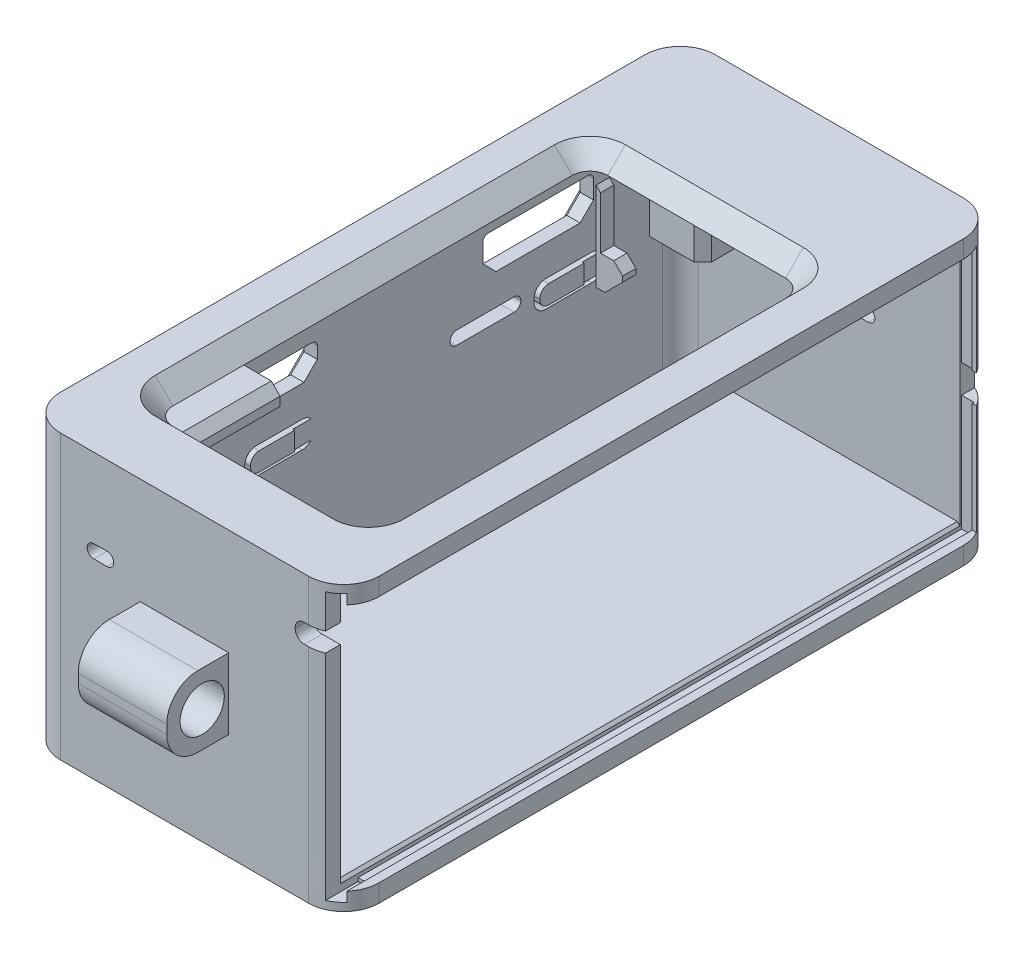
SolidWorks part; units mm, degrees
ref_plane "前视基准面" through (0, 0, 0) normal (0, 0, 1) x (1, 0, 0)
ref_plane "上视基准面" through (0, 0, 0) normal (0, 1, 0) x (1, 0, 0)
ref_plane "右视基准面" through (0, 0, 0) normal (1, 0, 0) x (0, 0, -1)
sketch "草图1" plane through (0, 0, 0) normal (1, 0, 0) x (0, 0, -1)
  line L1 (-54.0501, 29.0398) -> (19.9499, 29.0398)
  line L2 (-54.0501, 29.0398) -> (-54.0501, -2.9602)
  line L3 (-54.0501, -2.9602) -> (19.9499, -2.9602)
  line L4 (19.9499, 29.0398) -> (19.9499, -2.9602)
  dimension "D1" = 74
  dimension "D2" = 32
extrude "凸台-拉伸1" add sketch "草图1" along normal blind 36
sketch "草图2" plane through (36, 0, 0) normal (1, 0, 0) x (0, 0, -1)
  line L8 (17.9499, -0.9602) -> (17.9499, 27.0398)
  line L9 (-52.0501, -0.9602) -> (17.9499, -0.9602)
  line L10 (-52.0501, 27.0398) -> (-52.0501, -0.9602)
  line L11 (17.9499, 27.0398) -> (-52.0501, 27.0398)
  line L12 (17.9499, -0.9602) -> (17.9499, 27.0398)
  line L13 (-52.0501, -0.9602) -> (17.9499, -0.9602)
  line L14 (-52.0501, 27.0398) -> (-52.0501, -0.9602)
  line L15 (17.9499, 27.0398) -> (-52.0501, 27.0398)
  dimension "D1" = 2
extrude "切除-拉伸1" cut sketch "草图2" against normal blind 34
fillet "圆角1" radius 2 2 edges at (2, 13.0398, -17.9499) (2, 13.0398, 52.0501)
fillet "圆角2" radius 4 4 edges at (0, 13.0398, -19.9499) (0, 13.0398, 54.0501) (36, 13.0398, 54.0501) (36, 13.0398, -19.9499)
sketch "草图3" plane through (0, 29.0398, 0) normal (0, 1, 0) x (1, 0, 0)
  line L0 (32, 19.9499) -> (4, 19.9499) construction
  line L1 (29.8, 4.0599) -> (5.7, 4.0599)
  line L2 (29.8, 4.0599) -> (29.8, -45.0601)
  line L3 (29.8, -45.0601) -> (5.7, -45.0601)
  line L4 (5.7, 4.0599) -> (5.7, -45.0601)
  line L5 (36, 15.9499) -> (36, -50.0501) construction
  line L6 (32, -54.0501) -> (4, -54.0501) construction
  line L7 (0, 15.9499) -> (0, -50.0501) construction
  dimension "D1" = 15.89
  dimension "D2" = 6.2
  dimension "D3" = 8.99
  dimension "D4" = 5.7
extrude "切除-拉伸2" cut sketch "草图3" against normal blind 10
fillet "圆角3" radius 2 4 edges at (5.7, 28.0398, 45.0601) (29.8, 28.0398, 45.0601) (29.8, 28.0398, -4.0599) (5.7, 28.0398, -4.0599)
chamfer "倒角1" distance 2 angle 45 8 edges at (17.75, 29.0398, 45.0601) (29.2142, 29.0398, 44.4744) (6.2858, 29.0398, 44.4744) (29.8, 29.0398, 20.5001) (5.7, 29.0398, 20.5001) (29.2142, 29.0398, -3.4741) (6.2858, 29.0398, -3.4741) (17.75, 29.0398, -4.0599)
sketch "草图4" plane through (0, 0, 0) normal (-1, 0, 0) x (0, 0, 1)
  line L0 (-15.9499, 29.0398) -> (50.0501, 29.0398) construction
  line L1 (-8.1499, 22.4398) -> (4.3501, 22.4398)
  line L2 (-8.1499, 22.4398) -> (-8.1499, 18.2398)
  line L3 (-8.1499, 18.2398) -> (4.3501, 18.2398)
  line L4 (4.3501, 22.4398) -> (4.3501, 18.2398)
  line L5 (23.0501, 21.6812) -> (31.2501, 21.6812)
  line L6 (23.0501, 21.6812) -> (23.0501, 18.2398)
  line L7 (23.0501, 18.2398) -> (31.2501, 18.2398)
  line L8 (31.2501, 21.6812) -> (31.2501, 18.2398)
  line L9 (35.5501, 21.6398) -> (43.7501, 21.6398)
  line L10 (35.5501, 21.6398) -> (35.5501, 18.2398)
  line L11 (35.5501, 18.2398) -> (43.7501, 18.2398)
  line L12 (43.7501, 21.6398) -> (43.7501, 18.2398)
  line L13 (-9.2499, 14.7398) -> (-1.4499, 14.7398)
  line L14 (-9.2499, 14.7398) -> (-9.2499, 11.7398)
  line L15 (-9.2499, 11.7398) -> (-1.4499, 11.7398)
  line L16 (-1.4499, 14.7398) -> (-1.4499, 11.7398)
  line L17 (23.4501, 14.7398) -> (31.2501, 14.7398)
  line L18 (23.4501, 14.7398) -> (23.4501, 11.7398)
  line L19 (23.4501, 11.7398) -> (31.2501, 11.7398)
  line L20 (31.2501, 14.7398) -> (31.2501, 11.7398)
  line L21 (33.8696, 14.7398) -> (43.3696, 14.7398)
  line L22 (33.8696, 14.7398) -> (33.8696, 11.5398)
  line L23 (33.8696, 11.5398) -> (43.3696, 11.5398)
  line L24 (43.3696, 14.7398) -> (43.3696, 11.5398)
  line L25 (54.0501, 29.0398) -> (54.0501, -2.9602) construction
  line L27 (8.0501, 14.7398) -> (0.0501, 14.7398)
  line L28 (8.0501, 14.7398) -> (8.0501, 13.2398)
  line L29 (8.0501, 13.2398) -> (0.0501, 13.2398)
  line L30 (0.0501, 14.7398) -> (0.0501, 13.2398)
  dimension "D1" = 14.3
  dimension "D2" = 3.2
  dimension "D3" = 3
  dimension "D4" = 7.8
  dimension "D5" = 7.8
  dimension "D6" = 8.2
  dimension "D7" = 8.2
  dimension "D8" = 3.4
  dimension "D9" = 12.5
  dimension "D10" = 4.2
  dimension "D11" = 10.8
  dimension "D12" = 10.3
  dimension "D13" = 4.3
  dimension "D14" = 18.7
  dimension "D15" = 9.5
  dimension "D16" = 55.5
  dimension "D17" = 1.5
  dimension "D18" = 8
  dimension "D19" = 1.5
extrude "切除-拉伸3" cut sketch "草图4" against normal blind 10
fillet "圆角8" radius 0.75 4 edges at (1, 14.7398, 0.0501) (1, 14.7398, 8.0501) (1, 13.2398, 8.0501) (1, 13.2398, 0.0501)
sketch "草图5" plane through (2, 0, 0) normal (1, 0, 0) x (0, 0, -1)
  line L0 (-23.4501, 11.7398) -> (-23.4501, 14.7398) construction
  line L1 (-23.4501, 14.2898) -> (-30.8001, 14.2898)
  line L2 (-23.4501, 14.2898) -> (-23.4501, 12.1898)
  line L3 (-23.4501, 12.1898) -> (-30.8001, 12.1898)
  line L4 (-30.8001, 14.2898) -> (-30.8001, 12.1898)
  line L6 (1.8999, 12.1898) -> (9.2499, 12.1898)
  line L7 (1.8999, 12.1898) -> (1.8999, 14.2898)
  line L8 (1.8999, 14.2898) -> (9.2499, 14.2898)
  line L9 (9.2499, 12.1898) -> (9.2499, 14.2898)
  line L10 (-23.4501, 14.7398) -> (-31.2501, 14.7398) construction
  line L11 (-31.2501, 11.7398) -> (-23.4501, 11.7398) construction
  line L12 (-31.2501, 14.7398) -> (-31.2501, 11.7398) construction
  line L13 (9.2499, 14.7398) -> (1.4499, 14.7398) construction
  line L14 (1.4499, 11.7398) -> (9.2499, 11.7398) construction
  line L16 (1.4499, 14.7398) -> (1.4499, 11.7398) construction
  line L17 (9.2499, 11.7398) -> (9.2499, 14.7398) construction
  dimension "D1" = 0.45
  dimension "D2" = 0.45
  dimension "D3" = 0.45
  dimension "D4" = 0.45
  dimension "D5" = 0.45
  dimension "D7" = 0.45
extrude "凸台-拉伸2" add sketch "草图5" against normal blind 1.2
sketch "草图6" plane through (0.8, 0, 0) normal (-1, 0, 0) x (0, 0, 1)
  line L0 (-1.8999, 12.1898) -> (-9.2499, 12.1898) construction
  line L1 (-6.8999, 14.2898) -> (-1.8999, 14.2898)
  line L2 (-6.8999, 14.2898) -> (-6.8999, 12.1898)
  line L3 (-6.8999, 12.1898) -> (-1.8999, 12.1898)
  line L4 (-1.8999, 14.2898) -> (-1.8999, 12.1898)
  line L5 (30.8001, 12.1898) -> (23.4501, 12.1898) construction
  line L6 (30.8001, 14.2898) -> (25.8001, 14.2898)
  line L7 (30.8001, 14.2898) -> (30.8001, 12.1898)
  line L8 (30.8001, 12.1898) -> (25.8001, 12.1898)
  line L9 (25.8001, 14.2898) -> (25.8001, 12.1898)
  line L10 (-1.8999, 14.2898) -> (-1.8999, 12.1898) construction
  line L11 (-9.2499, 14.2898) -> (-1.8999, 14.2898) construction
  point P4 (-6.8999, 14.2898)
  point P18 (25.8001, 12.1898)
  dimension "D1" = 5
  dimension "D2" = 5
extrude "凸台-拉伸3" add sketch "草图6" along normal blind 1.5 and the other way blind 1.4
fillet "圆角4" radius 0.6 10 edges at (1, 11.5398, 33.8696) (1, 14.7398, 33.8696) (1, 14.7398, 43.3696) (1, 11.5398, 43.3696) (1, 21.6398, 35.5501) (1, 21.6398, 43.7501) (1, 21.6812, 31.2501) (1, 21.6812, 23.0501) (1, 22.4398, -8.1499) (1, 22.4398, 4.3501)
chamfer "倒角2" distance 1.5 angle 45 6 edges at (1, 18.2398, 43.7501) (1, 18.2398, 35.5501) (1, 18.2398, 31.2501) (1, 18.2398, 23.0501) (1, 18.2398, 4.3501) (1, 18.2398, -8.1499)
fillet "圆角5" radius 1 8 edges at (0.05, 12.1898, 25.8001) (0.05, 14.2898, 25.8001) (0.75, 12.1898, 30.8001) (0.75, 14.2898, 30.8001) (0.75, 12.1898, -1.8999) (0.75, 14.2898, -1.8999) (0.05, 12.1898, -6.8999) (0.05, 14.2898, -6.8999)
chamfer "倒角10" distance 0.2 angle 45 16 edges at (-0.7, 12.1898, 28.3001) (-0.7, 12.4827, 30.5072) (-0.7, 12.4827, 26.093) (-0.7, 13.9969, 30.5072) (-0.7, 13.9969, 26.093) (-0.7, 14.2898, 28.3001) (-0.7, 12.1898, -4.3999) (-0.7, 12.4827, -2.1928) (-0.7, 13.9969, -2.1928) (-0.7, 14.2898, -4.3999) (-0.7, 12.4827, -6.607) (-0.7, 13.9969, -6.607) (-0.7, 13.2398, 30.8001) (-0.7, 13.2398, 25.8001) (-0.7, 13.2398, -1.8999) (-0.7, 13.2398, -6.8999)
fillet "圆角6" radius 1.3 8 edges at (1, 14.7398, -1.4499) (1, 11.7398, -1.4499) (1, 11.7398, -9.2499) (1, 14.7398, -9.2499) (1, 14.7398, 23.4501) (1, 11.7398, 23.4501) (1, 11.7398, 31.2501) (1, 14.7398, 31.2501)
chamfer "倒角4" distance 0.5 angle 45 54 edges at (0, 11.7398, -5.3499) (0, 12.1206, -1.8306) (0, 12.1206, -8.8691) (0, 14.359, -1.8306) (0, 14.359, -8.8691) (0, 14.7398, -5.3499) (0, 18.9898, -7.3999) (0, 18.2398, -1.8999) (0, 18.9898, 3.6001) (0, 20.7898, 4.3501) (0, 20.7898, -8.1499) (0, 22.2641, 4.1744) (0, 22.2641, -7.9741) (0, 22.4398, -1.8999) (0, 11.5398, 38.6196) (0, 11.7155, 43.1938) (0, 11.7155, 34.0453) (0, 13.1398, 43.3696) (0, 13.1398, 33.8696) (0, 14.5641, 43.1938) (0, 14.5641, 34.0453) (0, 14.7398, 38.6196) (0, 11.7398, 27.3501) (0, 12.1206, 30.8694) (0, 12.1206, 23.8309) (0, 14.359, 30.8694) (0, 14.359, 23.8309) (0, 14.7398, 27.3501) (0, 20.4105, 23.0501) (0, 21.5055, 23.2259) (0, 21.6812, 27.1501) (0, 21.5055, 31.0744) (0, 18.9898, 23.8001) (0, 18.2398, 27.1501) (0, 18.9898, 30.5001) (0, 20.4105, 31.2501) (0, 18.9898, 43.0001) (0, 18.2398, 39.6501) (0, 18.9898, 36.3001) (0, 20.3898, 35.5501) (0, 21.4641, 35.7259) (0, 21.6398, 39.6501) (0, 20.3898, 43.7501) (0, 21.4641, 43.5744) (0, 13.4595, 7.8305) (0, 13.2398, 4.0501) (0, 13.4595, 0.2698) (0, 14.5201, 7.8305) (0, 14.7398, 4.0501) (0, 14.5201, 0.2698) (0, 13.2398, -1.4499) (0, 13.2398, -9.2499) (0, 13.2398, 31.2501) (0, 13.2398, 23.4501)
sketch "草图7" plane through (2, 0, 0) normal (1, 0, 0) x (0, 0, -1)
  line L0 (15.9499, 27.0398) -> (-50.0501, 27.0398) construction
  line L1 (-46.0501, 21.0398) -> (-44.5501, 21.0398)
  line L2 (-46.0501, 21.0398) -> (-46.0501, 11.0398)
  line L3 (-46.0501, 11.0398) -> (-44.5501, 11.0398)
  line L4 (-44.5501, 21.0398) -> (-44.5501, 11.0398)
  line L5 (8.4499, 21.0398) -> (9.9499, 21.0398)
  line L6 (8.4499, 21.0398) -> (8.4499, 11.0398)
  line L7 (8.4499, 11.0398) -> (9.9499, 11.0398)
  line L8 (9.9499, 21.0398) -> (9.9499, 11.0398)
  line L11 (17.9499, -0.9602) -> (17.9499, 27.0398) construction
  line L12 (-52.0501, 27.0398) -> (-52.0501, -0.9602) construction
  dimension "D1" = 6
  dimension "D2" = 10
  dimension "D3" = 1.5
  dimension "D4" = 1.5
  dimension "D5" = 8
  dimension "D6" = 6
extrude "凸台-拉伸4" add sketch "草图7" along normal blind 0.5
sketch "草图10" plane through (2.5, 0, 0) normal (1, 0, 0) x (0, 0, -1)
  line L1 (-46.0501, 11.0398) -> (-44.5501, 11.0398)
  line L2 (-46.0501, 11.0398) -> (-46.0501, 14.6398)
  line L3 (-46.0501, 14.6398) -> (-44.5501, 14.6398)
  line L4 (-44.5501, 11.0398) -> (-44.5501, 14.6398)
  line L7 (8.4499, 11.0398) -> (9.9499, 11.0398)
  line L8 (8.4499, 11.0398) -> (8.4499, 14.6398)
  line L9 (8.4499, 14.6398) -> (9.9499, 14.6398)
  line L10 (9.9499, 11.0398) -> (9.9499, 14.6398)
  dimension "D1" = 3.6
extrude "凸台-拉伸6" add sketch "草图10" along normal blind 2.5
chamfer "倒角7" distance 1 angle 45 2 edges at (5, 14.6398, -9.1999) (5, 14.6398, 45.3001)
chamfer "倒角8" distance 2 angle 45 2 edges at (5, 11.0398, 45.3001) (5, 11.0398, -9.1999)
chamfer "倒角5" distance 0.5 angle 45 2 edges at (2.5, 21.0398, 45.3001) (2.5, 21.0398, -9.1999)
sketch "草图8" plane through (2, 0, 0) normal (1, 0, 0) x (0, 0, -1)
  line L0 (15.9499, 29.0398) -> (-50.0501, 29.0398) construction
  line L1 (-44.2501, 22.2398) -> (-32.2501, 22.2398)
  line L2 (-44.2501, 22.2398) -> (-44.2501, 24.2398)
  line L3 (-44.2501, 24.2398) -> (-32.2501, 24.2398)
  line L4 (-32.2501, 22.2398) -> (-32.2501, 24.2398)
  line L5 (-54.0501, -2.9602) -> (-54.0501, 29.0398) construction
  dimension "D1" = 4.8
  dimension "D2" = 2
  dimension "D3" = 12
  dimension "D4" = 9.8
extrude "凸台-拉伸5" add sketch "草图8" along normal blind 5
chamfer "倒角6" distance 1 angle 45 1 edges at (7, 24.2398, 38.2501)
sketch "草图12" plane through (0, 0, 54.0501) normal (0, 0, 1) x (1, 0, 0)
  line L0 (4, -0.9602) -> (35.4641, -0.9602) construction
  line L1 (36, 27.0398) -> (33.6, 27.0398)
  line L2 (36, 27.0398) -> (36, -0.9602)
  line L3 (36, -0.9602) -> (33.6, -0.9602)
  line L4 (33.6, 27.0398) -> (33.6, -0.9602)
  dimension "D1" = 2.4
extrude "切除-拉伸5" cut sketch "草图12" against normal blind 10.8
sketch "草图11" plane through (0, -0.9602, 0) normal (0, 1, 0) x (1, 0, 0)
  line L0 (32, 19.9499) -> (4, 19.9499) construction
  line L1 (35, 17.9499) -> (33.6, 17.9499)
  line L2 (35, 17.9499) -> (35, -54.0501)
  line L3 (35, -54.0501) -> (33.6, -54.0501)
  line L4 (33.6, 17.9499) -> (33.6, -54.0501)
  line L5 (32, -54.0501) -> (4, -54.0501) construction
  line L6 (36, -50.0501) -> (36, 15.9499) construction
  dimension "D1" = 2
  dimension "D2" = 0
  dimension "D3" = 1
  dimension "D4" = 1.4
extrude "切除-拉伸4" cut sketch "草图11" against normal blind 0.7
sketch "草图13" plane through (0, 27.0398, 0) normal (0, -1, 0) x (1, 0, 0)
  line L10 (33.6, -17.9499) -> (35, -17.9499)
  line L11 (33.6, 54.0501) -> (33.6, -17.9499)
  line L12 (35, 54.0501) -> (33.6, 54.0501)
  line L13 (35, -17.9499) -> (35, 54.0501)
  line L14 (33.6, -17.9499) -> (35, -17.9499)
  line L15 (33.6, 54.0501) -> (33.6, -17.9499)
  line L16 (35, 54.0501) -> (33.6, 54.0501)
  line L17 (35, -17.9499) -> (35, 54.0501)
  dimension "D1" = 0
extrude "切除-拉伸6" cut sketch "草图13" against normal blind 0.7
sketch "草图14" plane through (0, -1.6602, 0) normal (0, 1, 0) x (1, 0, 0)
  line L1 (33.6, -54.0501) -> (35, -54.0501)
  line L2 (33.6, -54.0501) -> (33.6, -50.0501)
  line L3 (33.6, -50.0501) -> (35, -50.0501)
  line L4 (35, -54.0501) -> (35, -50.0501)
  line L5 (32, -54.0501) -> (4, -54.0501) construction
  line L6 (33.6, -53.7162) -> (33.6, 17.9499) construction
  dimension "D1" = 4
extrude "切除-拉伸7" cut sketch "草图14" against normal blind 0.4
sketch "草图15" plane through (0, 27.7398, 0) normal (0, -1, 0) x (1, 0, 0)
  line L3 (35, 50.0501) -> (35, 52.6959)
  line L4 (33.6, 50.0501) -> (35, 50.0501)
  line L5 (33.6, 53.7162) -> (33.6, 50.0501)
  line L7 (33.6, 50.0501) -> (35, 50.0501)
  line L8 (33.6, 53.7162) -> (33.6, 50.0501)
  line L10 (35, 50.0501) -> (35, 52.6959)
  arc A1 (35, 52.6959) -> (33.6, 53.7162) centre (32, 50.0501) ccw
  arc A2 (35, 52.6959) -> (33.6, 53.7162) centre (32, 50.0501) ccw
  dimension "D1" = 0
extrude "切除-拉伸8" cut sketch "草图15" against normal blind 0.4
sketch "草图16" plane through (0, 0, -17.9499) normal (0, 0, 1) x (1, 0, 0)
  line L0 (33.6, 28.1398) -> (33.6, -2.0602) construction
  line L1 (33.6, 27.7398) -> (35, 27.7398)
  line L2 (33.6, 27.7398) -> (33.6, -1.6602)
  line L3 (33.6, -1.6602) -> (35, -1.6602)
  line L4 (35, 27.7398) -> (35, -1.6602)
extrude "切除-拉伸9" cut sketch "草图16" against normal blind 0.2
chamfer "倒角9" distance 0.3 angle 45 2 edges at (33.6, 27.0398, 17.0501) (33.6, -0.9602, 17.0501)
ref_plane "基准面4" through (0, 13.0398, 0) normal (0, -1, 0) x (-1, 0, 0)
sketch "草图19" plane through (0, 0, -18.1499) normal (0, 0, 1) x (1, 0, 0)
  line L0 (35, 13.0398) -> (40.512, 13.0398) construction
  line L1 (35.4641, -0.9602) -> (35.4641, 27.0398) construction
  line L3 (34.3, 27.7398) -> (34.3, 24.7272) construction
  line L4 (33.6, 27.7398) -> (35, 27.7398) construction
  line L6 (33.6, 14.6398) -> (35.4641, 14.6398)
  line L7 (33.6, 14.6398) -> (33.6, 11.4398)
  line L8 (33.6, 11.4398) -> (35.4641, 11.4398)
  line L9 (35.4641, 14.6398) -> (35.4641, 11.4398)
  line L10 (33.6, 14.6398) -> (35.4641, 11.4398) construction
  line L11 (33.6, 11.4398) -> (35.4641, 14.6398) construction
  point P2 (34.3, 13.0398)
  point P10 (34.5321, 13.0398)
  point P13 (35.4641, 13.0398)
  point P16 (34.3, 27.7398)
  dimension "D1" = 3.2
extrude "切除-拉伸11" cut sketch "草图19" against normal blind 10 and the other way blind 2
sketch "草图20" plane through (0, 0, 54.0501) normal (0, 0, 1) x (1, 0, 0)
  line L0 (33.6, 24.2398) -> (33.6, 28.1198) construction
  line L1 (33.6, 24.2898) -> (30.5, 24.2898)
  line L2 (33.6, 24.2898) -> (33.6, 22.1398)
  line L3 (33.6, 22.1398) -> (30.5, 22.1398)
  line L4 (30.5, 24.2898) -> (30.5, 22.1398)
  line L5 (32, 29.0398) -> (4, 29.0398) construction
  dimension "D1" = 4.75
  dimension "D2" = 2.15
  dimension "D3" = 3.1
extrude "切除-拉伸12" cut sketch "草图20" against normal up to next
fillet "圆角9" radius 1.05 2 edges at (30.5, 24.2898, 53.0501) (30.5, 22.1398, 53.0501)
sketch "草图21" plane through (0, 0, -19.9499) normal (0, 0, -1) x (-1, 0, 0)
  line L0 (-25, 19.5398) -> (-14, 19.5398) construction
  line L1 (-25, 21.0398) -> (-14, 21.0398)
  line L2 (-25, 18.0398) -> (-14, 18.0398)
  line L3 (-4, -2.9602) -> (-4, 29.0398) construction
  line L4 (-32, 29.0398) -> (-4, 29.0398) construction
  arc A0 (-25, 21.0398) -> (-25, 18.0398) centre (-25, 19.5398) ccw
  arc A1 (-14, 18.0398) -> (-14, 21.0398) centre (-14, 19.5398) ccw
  point P2 (-19.5, 19.5398)
  dimension "D4" = 1.5
  dimension "D1" = 10
  dimension "D2" = 9.5
  dimension "D3" = 11
extrude "切除-拉伸13" cut sketch "草图21" against normal up to next
sketch "草图22" plane through (0, -2.9602, 0) normal (0, -1, 0) x (1, 0, 0)
  line L0 (7.7, -6.0599) -> (27.8, -6.0599) construction
  line B0 (13.068, 7.4573) -> (12.595, 6.6368)
  line B1 (12.595, 6.6368) -> (10.1389, 2.3799)
  line B2 (10.1389, 2.3799) -> (9.6602, 1.5593)
  line B3 (9.6602, -0.1617) -> (10.1389, -0.9823)
  line B4 (10.1389, -0.9823) -> (12.595, -5.2392)
  line B5 (12.595, -5.2392) -> (13.068, -6.0599)
  line B6 (14.5553, -6.9204) -> (21.3709, -6.9204)
  line B7 (22.8583, -6.0599) -> (23.3313, -5.2392)
  line B8 (23.3313, -5.2392) -> (25.7874, -0.9823)
  line B9 (25.7874, -0.9823) -> (26.2661, -0.1617)
  line B10 (26.2661, 1.5593) -> (25.7874, 2.3799)
  line B11 (25.7874, 2.3799) -> (23.3313, 6.6368)
  line B12 (23.3313, 6.6368) -> (22.8583, 7.4573)
  line B13 (21.3709, 8.3178) -> (14.5553, 8.3178)
  line B14 (13.7461, -4.9657) -> (10.703, 0.2999)
  line B15 (10.703, 1.1034) -> (13.7518, 6.3404)
  line B16 (14.4528, 6.3461) -> (17.4958, 1.2573)
  line B17 (22.6531, 2.8358) -> (22.9836, 2.2431)
  line B18 (23.0805, 2.1861) -> (24.7901, 2.1861)
  line B19 (24.887, 2.1292) -> (25.5138, 1.0236)
  line B20 (25.417, 0.8583) -> (20.14, 0.8583)
  line B21 (20.0431, 0.9153) -> (18.9775, 2.7959)
  line B22 (22.2998, 6.7393) -> (22.921, 5.6452)
  line B23 (22.8241, 5.4799) -> (20.311, 5.4799)
  line B24 (20.2141, 5.537) -> (19.5986, 6.6311)
  line B25 (19.6955, 6.7963) -> (22.2029, 6.7963)
  line B26 (21.6388, 2.7674) -> (21.9009, 2.2431)
  line B27 (21.7812, 2.1861) -> (20.4364, 2.1861)
  line B28 (20.3395, 2.2431) -> (20.0659, 2.7332)
  line B29 (15.034, 12.3126) -> (15.034, 10.4377)
  line B30 (15.034, 10.4377) -> (21.5989, 10.4377)
  line B31 (21.5989, 10.4377) -> (21.5989, 11.2698)
  line B32 (21.5989, 11.2698) -> (18.9946, 11.2698)
  line B33 (18.9946, 11.2698) -> (18.9946, 12.3582)
  line B34 (18.3221, 12.25) -> (18.3221, 11.2698)
  line B35 (18.3221, 11.2698) -> (15.7065, 11.2698)
  line B36 (15.7065, 11.2698) -> (15.7065, 12.2158)
  line B37 (16.7322, 15.8514) -> (21.5989, 15.8514)
  line B38 (21.5989, 15.8514) -> (21.5989, 16.6665)
  line B39 (21.5989, 16.6665) -> (16.7322, 16.6665)
  line B40 (16.7322, 16.6665) -> (16.7322, 15.8514)
  line B41 (17.8093, 21.3735) -> (17.4787, 20.5415)
  line B42 (16.6923, 21.6983) -> (15.6894, 22.4962)
  line B43 (18.6527, 19.265) -> (19.0117, 20.1141)
  line B44 (19.6613, 18.564) -> (20.7669, 17.658)
  line B45 (16.5043, 26.4795) -> (19.8437, 26.4795)
  line B46 (19.4562, 25.0377) -> (16.5043, 25.0377)
  line B47 (16.5043, 25.0377) -> (16.5043, 23.4478)
  line B48 (16.5043, 23.4478) -> (19.6556, 23.4478)
  line B49 (20.8979, 26.6277) -> (20.8979, 26.6618)
  line B50 (20.8979, 26.6618) -> (21.5989, 26.7759)
  line B51 (21.5989, 26.7759) -> (21.5989, 28.0751)
  line B52 (21.5989, 28.0751) -> (16.5043, 28.0751)
  line B53 (16.5043, 28.0751) -> (16.5043, 26.4795)
  line B54 (20.5959, 31.9274) -> (20.5959, 31.1239)
  line B55 (17.6554, 33.0216) -> (17.6554, 33.8079)
  line B56 (17.6554, 33.8079) -> (16.5043, 33.8079)
  line B57 (16.5043, 33.8079) -> (16.5043, 31.9388)
  line B58 (19.5474, 29.6878) -> (19.5816, 29.6878)
  line B59 (21.4108, 29.591) -> (21.4564, 29.591)
  line B60 (21.8154, 31.141) -> (21.8154, 31.6254)
  line B61 (17.0456, 34.2638) -> (18.0942, 34.8223)
  line B62 (21.086, 37.0676) -> (21.086, 37.1075)
  line B63 (21.086, 37.1075) -> (21.5989, 37.2214)
  line B64 (21.5989, 37.2214) -> (21.5989, 38.5207)
  line B65 (21.5989, 38.5207) -> (18.704, 38.5207)
  line B66 (19.2681, 36.9251) -> (20.083, 36.9251)
  line B67 (17.3876, 41.0111) -> (17.3876, 40.9769)
  line B68 (17.3876, 40.9769) -> (16.5043, 40.8686)
  line B69 (16.5043, 40.8686) -> (16.5043, 39.5693)
  line B70 (16.5043, 39.5693) -> (21.5989, 39.5693)
  line B71 (21.5989, 39.5693) -> (21.5989, 41.1536)
  line B72 (21.5989, 41.1536) -> (18.6869, 41.1536)
  line B73 (17.8548, 42.8118) -> (16.4815, 43.0796)
  line B74 (21.9009, 2.2431) -> (22.9836, 2.2431)
  line B75 (21.7812, 2.1861) -> (23.0805, 2.1861)
  spline B76 degree 3 poles (9.6602, 1.5593) (9.512, 1.2914) (9.4322, 0.9951) (9.4322, 0.6988) knots 3 3 3 3 4 4 4 4
  spline B77 degree 3 poles (9.4322, 0.6988) (9.4322, 0.4025) (9.512, 0.1061) (9.6602, -0.1617) knots 4 4 4 4 5 5 5 5
  spline B78 degree 3 poles (13.068, -6.0599) (13.3757, -6.5898) (13.9456, -6.9204) (14.5553, -6.9204) knots 8 8 8 8 9 9 9 9
  spline B79 degree 3 poles (21.3709, -6.9204) (21.9864, -6.9204) (22.5506, -6.5898) (22.8583, -6.0599) knots 10 10 10 10 11 11 11 11
  spline B80 degree 3 poles (26.2661, -0.1617) (26.4199, 0.1061) (26.494, 0.4025) (26.494, 0.6988) knots 14 14 14 14 15 15 15 15
  spline B81 degree 3 poles (26.494, 0.6988) (26.494, 0.9951) (26.4199, 1.2914) (26.2661, 1.5593) knots 15 15 15 15 16 16 16 16
  spline B82 degree 3 poles (22.8583, 7.4573) (22.5506, 7.993) (21.9864, 8.3178) (21.3709, 8.3178) knots 19 19 19 19 20 20 20 20
  spline B83 degree 3 poles (14.5553, 8.3178) (13.9456, 8.3178) (13.3757, 7.993) (13.068, 7.4573) knots 21 21 21 21 22 22 22 22
  spline B84 degree 2 poles (17.4958, 0.146) (14.5211, -5.0056) (14.5154, -5.017) knots 0 0 0 1 1 1
  spline B85 degree 3 poles (14.5154, -5.017) (14.3217, -5.2848) (13.9114, -5.2563) (13.7461, -4.9657) knots 1 1 1 1 2 2 2 2
  spline B86 degree 3 poles (10.703, 0.2999) (10.5606, 0.5449) (10.5606, 0.8527) (10.703, 1.1034) knots 3 3 3 3 4 4 4 4
  spline B87 degree 3 poles (13.7518, 6.3404) (13.9057, 6.6082) (14.2932, 6.6139) (14.4528, 6.3461) knots 5 5 5 5 6 6 6 6
  spline B88 degree 3 poles (17.4958, 1.2573) (17.6953, 0.9153) (17.6953, 0.4879) (17.4958, 0.146) knots 7 7 7 7 8 8 8 8
  spline B89 degree 3 poles (24.7901, 2.1861) (24.83, 2.1861) (24.8642, 2.169) (24.887, 2.1292) knots 3 3 3 3 4 4 4 4
  spline B90 degree 3 poles (25.5138, 1.0236) (25.5537, 0.9495) (25.5025, 0.8583) (25.417, 0.8583) knots 5 5 5 5 6 6 6 6
  spline B91 degree 3 poles (20.14, 0.8583) (20.1001, 0.8583) (20.0602, 0.8754) (20.0431, 0.9153) knots 7 7 7 7 8 8 8 8
  spline B92 degree 3 poles (18.9775, 2.7959) (18.2879, 4.0154) (18.1512, 5.024) (19.5189, 5.024) knots 9 9 9 9 10 10 10 10
  spline B93 degree 3 poles (19.5189, 5.024) (20.8353, 5.024) (21.9921, 4.004) (22.6531, 2.8358) knots 10 10 10 10 11 11 11 11
  spline B94 degree 3 poles (22.2029, 6.7963) (22.2428, 6.7963) (22.2827, 6.7735) (22.2998, 6.7393) knots 0 0 0 0 1 1 1 1
  spline B95 degree 3 poles (22.921, 5.6452) (22.9609, 5.5711) (22.9095, 5.4799) (22.8241, 5.4799) knots 2 2 2 2 3 3 3 3
  spline B96 degree 3 poles (20.311, 5.4799) (20.2711, 5.4799) (20.2369, 5.5027) (20.2141, 5.537) knots 4 4 4 4 5 5 5 5
  spline B97 degree 3 poles (19.5986, 6.6311) (19.5588, 6.7051) (19.61, 6.7963) (19.6955, 6.7963) knots 6 6 6 6 7 7 7 7
  spline B98 degree 3 poles (17.9289, 6.141) (17.6782, 6.5798) (17.7865, 6.8932) (18.1854, 6.8932) (18.5786, 6.8932) (19.0402, 6.5798) (19.2852, 6.141) knots 2 2 2 2 3 3 3 4 4 4 4
  spline B99 degree 3 poles (19.2852, 6.141) (19.5417, 5.6965) (19.4334, 5.3831) (19.0402, 5.3831) (18.6356, 5.3831) (18.1797, 5.6965) (17.9289, 6.141) knots 0 0 0 0 1 1 1 2 2 2 2
  spline B100 degree 3 poles (20.254, 3.7248) (20.7954, 3.7248) (21.274, 3.4171) (21.6388, 2.7674) knots 0 0 0 0 1 1 1 1
  spline B101 degree 3 poles (20.4364, 2.1861) (20.3965, 2.1861) (20.3566, 2.2089) (20.3395, 2.2431) knots 4 4 4 4 5 5 5 5
  spline B102 degree 3 poles (20.0659, 2.7332) (19.7012, 3.3714) (19.6955, 3.7248) (20.254, 3.7248) knots 6 6 6 6 7 7 7 7
  spline B103 degree 3 poles (18.9946, 12.3582) (18.9946, 13.7886) (18.345, 14.7745) (16.9602, 14.7745) knots 5 5 5 5 6 6 6 6
  spline B104 degree 3 poles (16.9602, 14.7745) (15.5241, 14.7745) (15.034, 13.7886) (15.034, 12.3126) knots 6 6 6 6 7 7 7 7
  spline B105 degree 3 poles (15.7065, 12.2158) (15.7065, 13.3669) (16.0085, 13.9482) (16.9602, 13.9482) knots 3 3 3 3 4 4 4 4
  spline B106 degree 3 poles (16.9602, 13.9482) (17.9004, 13.9482) (18.3221, 13.4068) (18.3221, 12.25) knots 4 4 4 4 5 5 5 5
  spline B107 degree 3 poles (15.7293, 16.2618) (15.7293, 16.5866) (15.507, 16.826) (15.205, 16.826) (14.8688, 16.826) (14.675, 16.5866) (14.675, 16.2618) knots 2 2 2 2 3 3 3 4 4 4 4
  spline B108 degree 3 poles (14.675, 16.2618) (14.675, 15.937) (14.8688, 15.6976) (15.205, 15.6976) (15.507, 15.6976) (15.7293, 15.937) (15.7293, 16.2618) knots 0 0 0 0 1 1 1 2 2 2 2
  spline B109 degree 3 poles (17.4787, 20.5415) (17.2451, 19.9545) (17.1026, 19.5328) (16.7322, 19.5328) knots 1 1 1 1 2 2 2 2
  spline B110 degree 3 poles (16.7322, 19.5328) (16.3789, 19.5328) (16.1794, 19.8349) (16.1794, 20.3306) knots 2 2 2 2 3 3 3 3
  spline B111 degree 3 poles (16.1794, 20.3306) (16.1794, 20.8492) (16.3561, 21.2595) (16.6923, 21.6983) knots 3 3 3 3 4 4 4 4
  spline B112 degree 3 poles (15.6894, 22.4962) (15.1024, 21.9149) (14.8061, 21.1) (14.8061, 20.3306) knots 5 5 5 5 6 6 6 6
  spline B113 degree 3 poles (14.8061, 20.3306) (14.8061, 18.9117) (15.7065, 17.9087) (16.8234, 17.9087) knots 6 6 6 6 7 7 7 7
  spline B114 degree 3 poles (16.8234, 17.9087) (17.7922, 17.9087) (18.3734, 18.564) (18.6527, 19.265) knots 7 7 7 7 8 8 8 8
  spline B115 degree 3 poles (19.0117, 20.1141) (19.251, 20.684) (19.3764, 21.0544) (19.7639, 21.0544) knots 9 9 9 9 10 10 10 10
  spline B116 degree 3 poles (19.7639, 21.0544) (20.1229, 21.0544) (20.3452, 20.7752) (20.3452, 20.1825) knots 10 10 10 10 11 11 11 11
  spline B117 degree 3 poles (20.3452, 20.1825) (20.3452, 19.6582) (20.0659, 19.037) (19.6613, 18.564) knots 11 11 11 11 12 12 12 12
  spline B118 degree 3 poles (20.7669, 17.658) (21.3994, 18.3475) (21.7243, 19.282) (21.7243, 20.1483) knots 13 13 13 13 14 14 14 14
  spline B119 degree 3 poles (21.7243, 20.1483) (21.7243, 21.761) (20.7498, 22.6955) (19.6385, 22.6955) knots 14 14 14 14 15 15 15 15
  spline B120 degree 3 poles (19.6385, 22.6955) (18.6983, 22.6955) (18.1398, 22.1998) (17.8093, 21.3735) knots 15 15 15 15 16 16 16 16
  spline B121 degree 3 poles (19.8437, 26.4795) (20.2198, 26.2117) (20.3623, 25.9894) (20.3623, 25.6304) knots 1 1 1 1 2 2 2 2
  spline B122 degree 3 poles (20.3623, 25.6304) (20.3623, 25.2258) (20.1628, 25.0377) (19.4562, 25.0377) knots 2 2 2 2 3 3 3 3
  spline B123 degree 3 poles (19.6556, 23.4478) (20.9264, 23.4478) (21.7243, 23.9208) (21.7243, 25.032) knots 6 6 6 6 7 7 7 7
  spline B124 degree 3 poles (21.7243, 25.032) (21.7243, 25.7273) (21.3994, 26.206) (20.8979, 26.6277) knots 7 7 7 7 8 8 8 8
  spline B125 degree 3 poles (20.5959, 31.1239) (20.5959, 30.5768) (20.4876, 30.3717) (20.254, 30.3717) knots 1 1 1 1 2 2 2 2
  spline B126 degree 3 poles (20.254, 30.3717) (20.083, 30.3717) (20.0032, 30.4115) (19.895, 30.5312) knots 2 2 2 2 3 3 3 3
  spline B127 degree 3 poles (19.895, 30.5312) (19.9576, 30.7535) (19.9862, 30.9586) (19.9862, 31.1296) knots 3 3 3 3 4 4 4 4
  spline B128 degree 3 poles (19.9862, 31.1296) (19.9862, 32.2579) (19.4676, 33.164) (18.2766, 33.164) knots 4 4 4 4 5 5 5 5
  spline B129 degree 3 poles (18.2766, 33.164) (18.0315, 33.164) (17.7979, 33.1013) (17.6554, 33.0216) knots 5 5 5 5 6 6 6 6
  spline B130 degree 3 poles (16.5043, 31.9388) (16.4188, 31.7051) (16.3789, 31.4259) (16.3789, 31.1296) knots 9 9 9 9 10 10 10 10
  spline B131 degree 3 poles (16.3789, 31.1296) (16.3789, 30.0298) (16.983, 28.9983) (18.231, 28.9983) knots 10 10 10 10 11 11 11 11
  spline B132 degree 3 poles (18.231, 28.9983) (18.8236, 28.9983) (19.2966, 29.3288) (19.5474, 29.6878) knots 11 11 11 11 12 12 12 12
  spline B133 degree 3 poles (19.5816, 29.6878) (19.8152, 29.3573) (20.1742, 29.1236) (20.5332, 29.1236) knots 13 13 13 13 14 14 14 14
  spline B134 degree 3 poles (20.5332, 29.1236) (20.9606, 29.1236) (21.2285, 29.3231) (21.4108, 29.591) knots 14 14 14 14 15 15 15 15
  spline B135 degree 3 poles (21.4564, 29.591) (21.6958, 29.1179) (22.0377, 28.8672) (22.4594, 28.8672) knots 16 16 16 16 17 17 17 17
  spline B136 degree 3 poles (22.4594, 28.8672) (23.3711, 28.8672) (23.7416, 29.8303) (23.7416, 31.0042) knots 17 17 17 17 18 18 18 18
  spline B137 degree 3 poles (23.7416, 31.0042) (23.7416, 32.7765) (22.978, 33.8878) (21.9009, 33.8878) knots 18 18 18 18 19 19 19 19
  spline B138 degree 3 poles (21.9009, 33.8878) (20.9777, 33.8878) (20.5959, 33.1811) (20.5959, 31.9274) knots 19 19 19 19 20 20 20 20
  spline B139 degree 3 poles (19.0288, 31.1296) (19.0288, 30.7649) (18.7609, 30.4857) (18.231, 30.4857) (17.7124, 30.4857) (17.4446, 30.7649) (17.4446, 31.1296) knots 2 2 2 2 3 3 3 4 4 4 4
  spline B140 degree 3 poles (17.4446, 31.1296) (17.4446, 31.5057) (17.7124, 31.7735) (18.231, 31.7735) (18.7609, 31.7735) (19.0288, 31.5057) (19.0288, 31.1296) knots 0 0 0 0 1 1 1 2 2 2 2
  spline B141 degree 3 poles (22.7443, 31.2549) (22.7443, 30.5996) (22.5676, 30.1722) (22.2086, 30.1722) knots 0 0 0 0 1 1 1 1
  spline B142 degree 3 poles (22.2086, 30.1722) (22.0377, 30.1722) (21.8952, 30.252) (21.7527, 30.4115) knots 1 1 1 1 2 2 2 2
  spline B143 degree 3 poles (21.7527, 30.4115) (21.7983, 30.5768) (21.8154, 30.7706) (21.8154, 31.141) knots 2 2 2 2 3 3 3 3
  spline B144 degree 3 poles (21.8154, 31.6254) (21.8154, 32.0983) (21.8781, 32.3662) (22.1801, 32.3662) knots 4 4 4 4 5 5 5 5
  spline B145 degree 3 poles (22.1801, 32.3662) (22.505, 32.3662) (22.7443, 31.9104) (22.7443, 31.2549) knots 5 5 5 5 6 6 6 6
  spline B146 degree 3 poles (16.3789, 36.4579) (16.3789, 35.6657) (16.6467, 34.9363) (17.0456, 34.2638) knots 0 0 0 0 1 1 1 1
  spline B147 degree 3 poles (18.0942, 34.8223) (17.8093, 35.3296) (17.6497, 35.7512) (17.6497, 36.1558) knots 2 2 2 2 3 3 3 3
  spline B148 degree 3 poles (17.6497, 36.1558) (17.6497, 36.6744) (17.889, 36.891) (18.2994, 36.9251) knots 3 3 3 3 4 4 4 4
  spline B149 degree 3 poles (18.2994, 36.9251) (18.5159, 34.9363) (19.0971, 34.0928) (20.1742, 34.0928) knots 4 4 4 4 5 5 5 5
  spline B150 degree 3 poles (20.1742, 34.0928) (21.0233, 34.0928) (21.7243, 34.6684) (21.7243, 35.6088) knots 5 5 5 5 6 6 6 6
  spline B151 degree 3 poles (21.7243, 35.6088) (21.7243, 36.1729) (21.4621, 36.6459) (21.086, 37.0676) knots 6 6 6 6 7 7 7 7
  spline B152 degree 3 poles (18.704, 38.5207) (17.1083, 38.5207) (16.3789, 37.7742) (16.3789, 36.4579) knots 11 11 11 11 12 12 12 12
  spline B153 degree 3 poles (20.083, 36.9251) (20.3338, 36.6915) (20.4876, 36.4806) (20.4876, 36.1558) knots 0 0 0 0 1 1 1 1
  spline B154 degree 3 poles (20.4876, 36.1558) (20.4876, 35.8253) (20.3452, 35.6088) (20.0488, 35.6088) knots 1 1 1 1 2 2 2 2
  spline B155 degree 3 poles (20.0488, 35.6088) (19.6898, 35.6088) (19.4049, 35.9336) (19.2681, 36.9251) knots 2 2 2 2 3 3 3 3
  spline B156 degree 3 poles (16.3789, 42.4642) (16.3789, 41.9513) (16.7094, 41.3872) (17.3876, 41.0111) knots 0 0 0 0 1 1 1 1
  spline B157 degree 3 poles (18.6869, 41.1536) (18.0144, 41.4214) (17.7751, 41.8773) (17.7751, 42.2534) knots 7 7 7 7 8 8 8 8
  spline B158 degree 3 poles (17.7751, 42.2534) (17.7751, 42.4813) (17.8093, 42.6295) (17.8548, 42.8118) knots 8 8 8 8 9 9 9 9
  spline B159 degree 3 poles (16.4815, 43.0796) (16.4188, 42.9372) (16.3789, 42.7663) (16.3789, 42.4642) knots 10 10 10 10 11 11 11 11
sketch_block_instance "块1-1"
sketch_block "块1"
extrude "切除-拉伸14" cut sketch "草图22" against normal blind 0.3
ref_plane "基准面5" through (13, 0, 0) normal (1, 0, 0) x (0, 0, -1)
sketch "草图23" plane through (13, 0, 0) normal (1, 0, 0) x (0, 0, -1)
  line L0 (-54.0501, -2.9602) -> (-54.0501, 22.1398) construction
  line L1 (-54.0501, 17.0398) -> (-61.0501, 17.0398)
  line L2 (-54.0501, 17.0398) -> (-54.0501, 9.0398)
  line L3 (-54.0501, 9.0398) -> (-61.0501, 9.0398)
  line L4 (-61.0501, 17.0398) -> (-61.0501, 9.0398)
  dimension "D1" = 12
  dimension "D2" = 8
  dimension "D3" = 7
extrude "凸台-拉伸7" add sketch "草图23" along normal blind 10
sketch "草图24" plane through (23, 0, 0) normal (1, 0, 0) x (0, 0, -1)
  line L0 (-61.0501, 17.0398) -> (-61.0501, 9.0398) construction
  line L1 (-54.0501, 17.0398) -> (-61.0501, 17.0398) construction
  circle A0 centre (-57.0501, 13.0398) radius 2.5
  dimension "D1" = 5
  dimension "D2" = 4
  dimension "D3" = 4
extrude "切除-拉伸15" cut sketch "草图24" against normal through all
fillet "圆角10" radius 3.5 2 edges at (18, 9.0398, 61.0501) (18, 17.0398, 61.0501)
ref_plane "基准面6" through (0, 15, 0) normal (0, 1, 0) x (1, 0, 0)
sketch "草图25" plane through (0, 15, 0) normal (0, 1, 0) x (1, 0, 0)
  line L0 (8, 14.4999) -> (8, 19.1472)
  line L1 (0, -50.0501) -> (0, 15.9499) construction
  line L2 (0, 15.9499) -> (0, -50.0501) construction
  line L3 (1, 14.4999) -> (1, 17.0058)
  line L4 (32, 19.9499) -> (4, 19.9499) construction
  line L5 (1, 17.0058) -> (3.1414, 19.1472)
  line L7 (8, 14.4999) -> (1, 14.4999)
  line L8 (3.1414, 19.1472) -> (8, 19.1472)
  line L9 (8, -50.5366) -> (1, -50.5366)
  line L11 (1, -50.5366) -> (3.1414, -52.9483)
  line L12 (3.1414, -52.9483) -> (8, -52.9483)
  line L13 (8, -52.9483) -> (8, -50.5366)
  dimension "D1" = 8
  dimension "D2" = 5.45
  dimension "D3" = 1
extrude "凸台-拉伸8" add sketch "草图25" along normal blind 5 and the other way blind 2
chamfer "倒角11" distance 1 angle 45 2 edges at (8, 16.5, 50.5366) (8, 16.5, -14.4999)
sketch "草图26" plane through (0, 0, -19.9499) normal (0, 0, -1) x (-1, 0, 0)
  line L0 (20.185, 15) -> (-20.185, 15) construction
  line L1 (-24, 15) -> (-21, 15)
  line L2 (-24, 15) -> (-24, 13.5)
  line L3 (-24, 13.5) -> (-21, 13.5)
  line L4 (-21, 15) -> (-21, 13.5)
  line L5 (-32, 29.0398) -> (-32, -2.9602) construction
  dimension "D1" = 1.5
  dimension "D2" = 3
  dimension "D3" = 8
extrude "切除-拉伸16" cut sketch "草图26" against normal up to next
fillet "圆角11" radius 0.75 4 edges at (21, 13.5, -18.9499) (21, 15, -18.9499) (24, 15, -18.9499) (24, 13.5, -18.9499)
sketch "草图27" plane through (0, 0, 54.0501) normal (0, 0, 1) x (1, 0, 0)
  line L1 (7, 18.6) -> (10, 18.6)
  line L2 (7, 18.6) -> (7, 20.1)
  line L3 (7, 20.1) -> (10, 20.1)
  line L4 (10, 18.6) -> (10, 20.1)
  line L6 (20.185, 15) -> (-20.185, 15) construction
  line L7 (4, 29.0398) -> (4, -2.9602) construction
  dimension "D1" = 3
  dimension "D2" = 1.5
  dimension "D3" = 3.6
  dimension "D4" = 3
extrude "切除-拉伸17" cut sketch "草图27" against normal up to next
fillet "圆角12" radius 0.75 4 edges at (10, 20.1, 53.0501) (10, 18.6, 53.0501) (7, 20.1, 53.0501) (7, 18.6, 52.2934)
